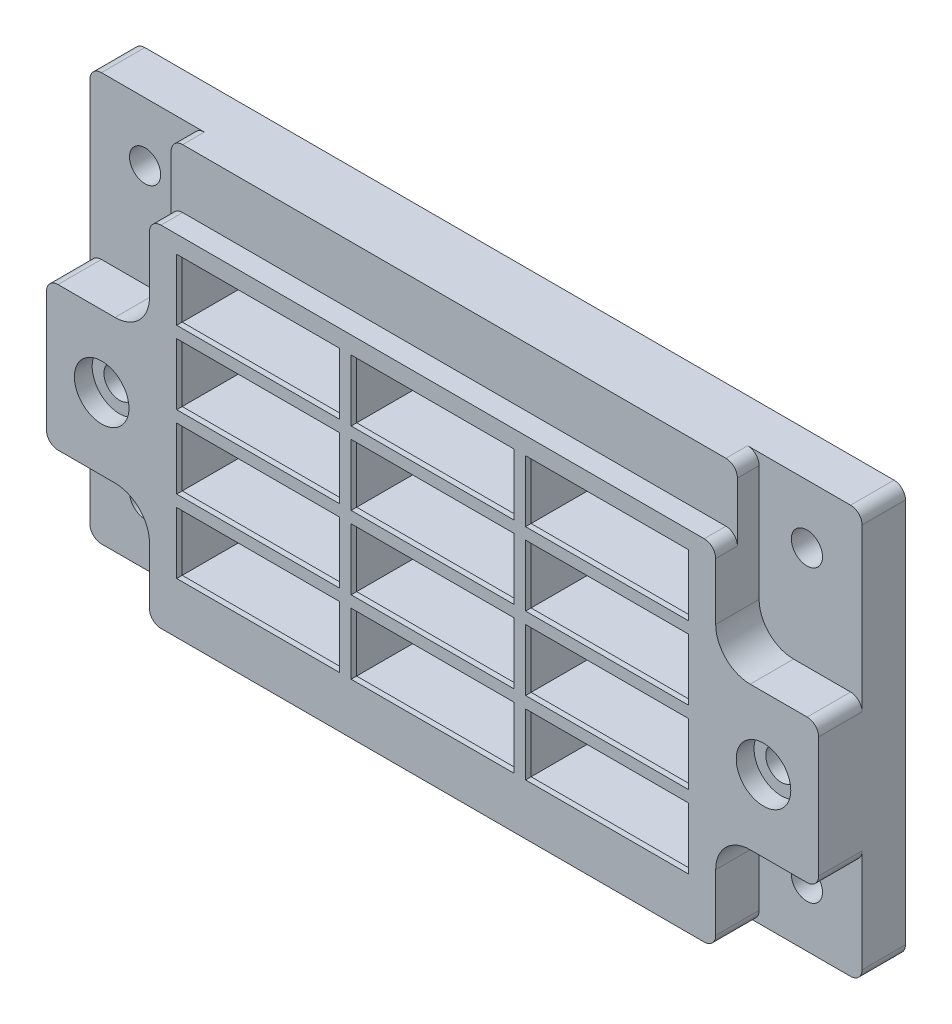
SolidWorks part; units mm, degrees
ref_plane "Front Plane" through (0, 0, 0) normal (0, 0, 1) x (1, 0, 0)
ref_plane "Top Plane" through (0, 0, 0) normal (0, 1, 0) x (1, 0, 0)
ref_plane "Right Plane" through (0, 0, 0) normal (1, 0, 0) x (0, 0, -1)
sketch "Sketch1" plane through (0, 0, 0) normal (0, 0, 1) x (1, 0, 0)
  line L4 (-3157.9913, 1122.9957) -> (-3054.4863, 1122.9957)
  line L5 (-3159.5788, 1177.7962) -> (-3159.5788, 1124.5832)
  line L6 (-3054.4863, 1179.3837) -> (-3157.9913, 1179.3837)
  line L7 (-3052.8988, 1124.5832) -> (-3052.8988, 1177.7962)
  line L8 (-3157.9913, 1122.9957) -> (-3054.4863, 1122.9957)
  line L9 (-3159.5788, 1177.7962) -> (-3159.5788, 1124.5832)
  line L10 (-3054.4863, 1179.3837) -> (-3157.9913, 1179.3837)
  line L11 (-3052.8988, 1124.5832) -> (-3052.8988, 1177.7962)
  arc A4 (-3159.5788, 1124.5832) -> (-3157.9913, 1122.9957) centre (-3157.9913, 1124.5832) ccw
  arc A5 (-3157.9913, 1179.3837) -> (-3159.5788, 1177.7962) centre (-3157.9913, 1177.7962) ccw
  arc A6 (-3052.8988, 1177.7962) -> (-3054.4863, 1179.3837) centre (-3054.4863, 1177.7962) ccw
  arc A7 (-3054.4863, 1122.9957) -> (-3052.8988, 1124.5832) centre (-3054.4863, 1124.5832) ccw
  arc A8 (-3159.5788, 1124.5832) -> (-3157.9913, 1122.9957) centre (-3157.9913, 1124.5832) ccw
  arc A9 (-3157.9913, 1179.3837) -> (-3159.5788, 1177.7962) centre (-3157.9913, 1177.7962) ccw
  arc A10 (-3052.8988, 1177.7962) -> (-3054.4863, 1179.3837) centre (-3054.4863, 1177.7962) ccw
  arc A11 (-3054.4863, 1122.9957) -> (-3052.8988, 1124.5832) centre (-3054.4863, 1124.5832) ccw
  dimension "D1" = 0
extrude "Boss-Extrude1" add sketch "Sketch1" along normal up to surface (6 mm away)
sketch "Sketch2" plane through (0, 0, 6) normal (0, 0, 1) x (1, 0, 0)
  line L0 (-3143.7673, 1122.9957) -> (-3068.7103, 1122.9957) construction
  line L1 (-3067.1228, 1124.5832) -> (-3067.1228, 1132.4572) construction
  line L2 (-3062.3603, 1137.2197) -> (-3054.4863, 1137.2197) construction
  line L3 (-3052.8988, 1138.8072) -> (-3052.8988, 1155.4442) construction
  line L4 (-3054.4863, 1157.0317) -> (-3062.3603, 1157.0317) construction
  line L5 (-3067.1228, 1161.7942) -> (-3067.1228, 1169.6682) construction
  line L7 (-3145.3548, 1169.6682) -> (-3145.3548, 1161.7942) construction
  line L8 (-3150.1173, 1157.0317) -> (-3157.9913, 1157.0317) construction
  line L9 (-3159.5788, 1155.4442) -> (-3159.5788, 1138.8072) construction
  line L10 (-3157.9913, 1137.2197) -> (-3150.1173, 1137.2197) construction
  line L11 (-3145.3548, 1132.4572) -> (-3145.3548, 1124.5832) construction
  line L12 (-3067.1228, 1169.6682) -> (-3067.1228, 1177.7962) construction
  line L13 (-3068.7103, 1179.3837) -> (-3143.7673, 1179.3837) construction
  line L14 (-3145.3548, 1177.7962) -> (-3145.3548, 1169.6682) construction
  line L16 (-3143.7673, 1122.9957) -> (-3068.7103, 1122.9957)
  line L17 (-3067.1228, 1124.5832) -> (-3067.1228, 1132.4572)
  line L18 (-3062.3603, 1137.2197) -> (-3054.4863, 1137.2197)
  line L19 (-3052.8988, 1138.8072) -> (-3052.8988, 1155.4442)
  line L20 (-3054.4863, 1157.0317) -> (-3062.3603, 1157.0317)
  line L21 (-3067.1228, 1161.7942) -> (-3067.1228, 1169.6682)
  line L23 (-3145.3548, 1169.6682) -> (-3145.3548, 1161.7942)
  line L24 (-3150.1173, 1157.0317) -> (-3157.9913, 1157.0317)
  line L25 (-3159.5788, 1155.4442) -> (-3159.5788, 1138.8072)
  line L26 (-3157.9913, 1137.2197) -> (-3150.1173, 1137.2197)
  line L27 (-3145.3548, 1132.4572) -> (-3145.3548, 1124.5832)
  line L28 (-3067.1228, 1169.6682) -> (-3067.1228, 1177.7962)
  line L29 (-3068.7103, 1179.3837) -> (-3143.7673, 1179.3837)
  line L30 (-3145.3548, 1177.7962) -> (-3145.3548, 1169.6682)
  arc A0 (-3145.3548, 1124.5832) -> (-3143.7673, 1122.9957) centre (-3143.7673, 1124.5832) ccw construction
  arc A1 (-3068.7103, 1122.9957) -> (-3067.1228, 1124.5832) centre (-3068.7103, 1124.5832) ccw construction
  arc A2 (-3062.3603, 1137.2197) -> (-3067.1228, 1132.4572) centre (-3062.3603, 1132.4572) ccw construction
  arc A3 (-3054.4863, 1137.2197) -> (-3052.8988, 1138.8072) centre (-3054.4863, 1138.8072) ccw construction
  arc A4 (-3052.8988, 1155.4442) -> (-3054.4863, 1157.0317) centre (-3054.4863, 1155.4442) ccw construction
  arc A5 (-3067.1228, 1161.7942) -> (-3062.3603, 1157.0317) centre (-3062.3603, 1161.7942) ccw construction
  arc A8 (-3150.1173, 1157.0317) -> (-3145.3548, 1161.7942) centre (-3150.1173, 1161.7942) ccw construction
  arc A9 (-3157.9913, 1157.0317) -> (-3159.5788, 1155.4442) centre (-3157.9913, 1155.4442) ccw construction
  arc A10 (-3159.5788, 1138.8072) -> (-3157.9913, 1137.2197) centre (-3157.9913, 1138.8072) ccw construction
  arc A11 (-3145.3548, 1132.4572) -> (-3150.1173, 1137.2197) centre (-3150.1173, 1132.4572) ccw construction
  arc A13 (-3067.1228, 1177.7962) -> (-3068.7103, 1179.3837) centre (-3068.7103, 1177.7962) ccw construction
  arc A14 (-3143.7673, 1179.3837) -> (-3145.3548, 1177.7962) centre (-3143.7673, 1177.7962) ccw construction
  arc A16 (-3145.3548, 1124.5832) -> (-3143.7673, 1122.9957) centre (-3143.7673, 1124.5832) ccw
  arc A17 (-3068.7103, 1122.9957) -> (-3067.1228, 1124.5832) centre (-3068.7103, 1124.5832) ccw
  arc A18 (-3062.3603, 1137.2197) -> (-3067.1228, 1132.4572) centre (-3062.3603, 1132.4572) ccw
  arc A19 (-3054.4863, 1137.2197) -> (-3052.8988, 1138.8072) centre (-3054.4863, 1138.8072) ccw
  arc A20 (-3052.8988, 1155.4442) -> (-3054.4863, 1157.0317) centre (-3054.4863, 1155.4442) ccw
  arc A21 (-3067.1228, 1161.7942) -> (-3062.3603, 1157.0317) centre (-3062.3603, 1161.7942) ccw
  arc A24 (-3150.1173, 1157.0317) -> (-3145.3548, 1161.7942) centre (-3150.1173, 1161.7942) ccw
  arc A25 (-3157.9913, 1157.0317) -> (-3159.5788, 1155.4442) centre (-3157.9913, 1155.4442) ccw
  arc A26 (-3159.5788, 1138.8072) -> (-3157.9913, 1137.2197) centre (-3157.9913, 1138.8072) ccw
  arc A27 (-3145.3548, 1132.4572) -> (-3150.1173, 1137.2197) centre (-3150.1173, 1132.4572) ccw
  arc A29 (-3067.1228, 1177.7962) -> (-3068.7103, 1179.3837) centre (-3068.7103, 1177.7962) ccw
  arc A30 (-3143.7673, 1179.3837) -> (-3145.3548, 1177.7962) centre (-3143.7673, 1177.7962) ccw
extrude "Boss-Extrude2" add sketch "Sketch2" along normal up to surface (3 mm away)
sketch "Sketch3" plane through (0, 0, 9) normal (0, 0, 1) x (1, 0, 0)
  line L12 (-3143.7673, 1122.9957) -> (-3068.7103, 1122.9957)
  line L13 (-3067.1228, 1124.5832) -> (-3067.1228, 1132.4572)
  line L14 (-3062.3603, 1137.2197) -> (-3054.4863, 1137.2197)
  line L15 (-3052.8988, 1138.8072) -> (-3052.8988, 1155.4442)
  line L16 (-3054.4863, 1157.0317) -> (-3062.3603, 1157.0317)
  line L17 (-3067.1228, 1161.7942) -> (-3067.1228, 1169.6682)
  line L18 (-3068.7103, 1171.2557) -> (-3143.7673, 1171.2557)
  line L19 (-3145.3548, 1169.6682) -> (-3145.3548, 1161.7942)
  line L20 (-3150.1173, 1157.0317) -> (-3157.9913, 1157.0317)
  line L21 (-3159.5788, 1155.4442) -> (-3159.5788, 1138.8072)
  line L22 (-3157.9913, 1137.2197) -> (-3150.1173, 1137.2197)
  line L23 (-3145.3548, 1132.4572) -> (-3145.3548, 1124.5832)
  line L24 (-3143.7673, 1122.9957) -> (-3068.7103, 1122.9957)
  line L25 (-3067.1228, 1124.5832) -> (-3067.1228, 1132.4572)
  line L26 (-3062.3603, 1137.2197) -> (-3054.4863, 1137.2197)
  line L27 (-3052.8988, 1138.8072) -> (-3052.8988, 1155.4442)
  line L28 (-3054.4863, 1157.0317) -> (-3062.3603, 1157.0317)
  line L29 (-3067.1228, 1161.7942) -> (-3067.1228, 1169.6682)
  line L30 (-3068.7103, 1171.2557) -> (-3143.7673, 1171.2557)
  line L31 (-3145.3548, 1169.6682) -> (-3145.3548, 1161.7942)
  line L32 (-3150.1173, 1157.0317) -> (-3157.9913, 1157.0317)
  line L33 (-3159.5788, 1155.4442) -> (-3159.5788, 1138.8072)
  line L34 (-3157.9913, 1137.2197) -> (-3150.1173, 1137.2197)
  line L35 (-3145.3548, 1132.4572) -> (-3145.3548, 1124.5832)
  arc A12 (-3145.3548, 1124.5832) -> (-3143.7673, 1122.9957) centre (-3143.7673, 1124.5832) ccw
  arc A13 (-3068.7103, 1122.9957) -> (-3067.1228, 1124.5832) centre (-3068.7103, 1124.5832) ccw
  arc A14 (-3062.3603, 1137.2197) -> (-3067.1228, 1132.4572) centre (-3062.3603, 1132.4572) ccw
  arc A15 (-3054.4863, 1137.2197) -> (-3052.8988, 1138.8072) centre (-3054.4863, 1138.8072) ccw
  arc A16 (-3052.8988, 1155.4442) -> (-3054.4863, 1157.0317) centre (-3054.4863, 1155.4442) ccw
  arc A17 (-3067.1228, 1161.7942) -> (-3062.3603, 1157.0317) centre (-3062.3603, 1161.7942) ccw
  arc A18 (-3067.1228, 1169.6682) -> (-3068.7103, 1171.2557) centre (-3068.7103, 1169.6682) ccw
  arc A19 (-3143.7673, 1171.2557) -> (-3145.3548, 1169.6682) centre (-3143.7673, 1169.6682) ccw
  arc A20 (-3150.1173, 1157.0317) -> (-3145.3548, 1161.7942) centre (-3150.1173, 1161.7942) ccw
  arc A21 (-3157.9913, 1157.0317) -> (-3159.5788, 1155.4442) centre (-3157.9913, 1155.4442) ccw
  arc A22 (-3159.5788, 1138.8072) -> (-3157.9913, 1137.2197) centre (-3157.9913, 1138.8072) ccw
  arc A23 (-3145.3548, 1132.4572) -> (-3150.1173, 1137.2197) centre (-3150.1173, 1132.4572) ccw
  arc A24 (-3145.3548, 1124.5832) -> (-3143.7673, 1122.9957) centre (-3143.7673, 1124.5832) ccw
  arc A25 (-3068.7103, 1122.9957) -> (-3067.1228, 1124.5832) centre (-3068.7103, 1124.5832) ccw
  arc A26 (-3062.3603, 1137.2197) -> (-3067.1228, 1132.4572) centre (-3062.3603, 1132.4572) ccw
  arc A27 (-3054.4863, 1137.2197) -> (-3052.8988, 1138.8072) centre (-3054.4863, 1138.8072) ccw
  arc A28 (-3052.8988, 1155.4442) -> (-3054.4863, 1157.0317) centre (-3054.4863, 1155.4442) ccw
  arc A29 (-3067.1228, 1161.7942) -> (-3062.3603, 1157.0317) centre (-3062.3603, 1161.7942) ccw
  arc A30 (-3067.1228, 1169.6682) -> (-3068.7103, 1171.2557) centre (-3068.7103, 1169.6682) ccw
  arc A31 (-3143.7673, 1171.2557) -> (-3145.3548, 1169.6682) centre (-3143.7673, 1169.6682) ccw
  arc A32 (-3150.1173, 1157.0317) -> (-3145.3548, 1161.7942) centre (-3150.1173, 1161.7942) ccw
  arc A33 (-3157.9913, 1157.0317) -> (-3159.5788, 1155.4442) centre (-3157.9913, 1155.4442) ccw
  arc A34 (-3159.5788, 1138.8072) -> (-3157.9913, 1137.2197) centre (-3157.9913, 1138.8072) ccw
  arc A35 (-3145.3548, 1132.4572) -> (-3150.1173, 1137.2197) centre (-3150.1173, 1132.4572) ccw
  dimension "D1" = 0
extrude "Boss-Extrude3" add sketch "Sketch3" along normal up to surface (3 mm away)
sketch "Sketch4" plane through (0, 0, 12) normal (0, 0, 1) x (1, 0, 0)
  line L0 (-3070.8888, 1130.0557) -> (-3070.8888, 1138.5557) construction
  line L1 (-3070.8888, 1138.5557) -> (-3093.3888, 1138.5557) construction
  line L2 (-3093.3888, 1138.5557) -> (-3093.3888, 1130.0557) construction
  line L3 (-3093.3888, 1130.0557) -> (-3070.8888, 1130.0557) construction
  line L4 (-3094.9888, 1138.5557) -> (-3117.4888, 1138.5557) construction
  line L5 (-3117.4888, 1138.5557) -> (-3117.4888, 1130.0557) construction
  line L6 (-3117.4888, 1130.0557) -> (-3094.9888, 1130.0557) construction
  line L7 (-3094.9888, 1130.0557) -> (-3094.9888, 1138.5557) construction
  line L8 (-3119.0888, 1138.5557) -> (-3141.5888, 1138.5557) construction
  line L9 (-3141.5888, 1138.5557) -> (-3141.5888, 1130.0557) construction
  line L10 (-3141.5888, 1130.0557) -> (-3119.0888, 1130.0557) construction
  line L11 (-3119.0888, 1130.0557) -> (-3119.0888, 1138.5557) construction
  line L12 (-3119.0888, 1140.1557) -> (-3119.0888, 1148.6557) construction
  line L13 (-3119.0888, 1148.6557) -> (-3141.5888, 1148.6557) construction
  line L14 (-3141.5888, 1148.6557) -> (-3141.5888, 1140.1557) construction
  line L15 (-3141.5888, 1140.1557) -> (-3119.0888, 1140.1557) construction
  line L16 (-3094.9888, 1140.1557) -> (-3094.9888, 1148.6557) construction
  line L17 (-3094.9888, 1148.6557) -> (-3117.4888, 1148.6557) construction
  line L18 (-3117.4888, 1148.6557) -> (-3117.4888, 1140.1557) construction
  line L19 (-3117.4888, 1140.1557) -> (-3094.9888, 1140.1557) construction
  line L20 (-3070.8888, 1148.6557) -> (-3093.3888, 1148.6557) construction
  line L21 (-3093.3888, 1148.6557) -> (-3093.3888, 1140.1557) construction
  line L22 (-3093.3888, 1140.1557) -> (-3070.8888, 1140.1557) construction
  line L23 (-3070.8888, 1140.1557) -> (-3070.8888, 1148.6557) construction
  line L24 (-3070.8888, 1158.7557) -> (-3093.3888, 1158.7557) construction
  line L25 (-3093.3888, 1158.7557) -> (-3093.3888, 1150.2557) construction
  line L26 (-3093.3888, 1150.2557) -> (-3070.8888, 1150.2557) construction
  line L27 (-3070.8888, 1150.2557) -> (-3070.8888, 1158.7557) construction
  line L28 (-3094.9888, 1150.2557) -> (-3094.9888, 1158.7557) construction
  line L29 (-3094.9888, 1158.7557) -> (-3117.4888, 1158.7557) construction
  line L30 (-3117.4888, 1158.7557) -> (-3117.4888, 1150.2557) construction
  line L31 (-3117.4888, 1150.2557) -> (-3094.9888, 1150.2557) construction
  line L32 (-3119.0888, 1150.2557) -> (-3119.0888, 1158.7557) construction
  line L33 (-3119.0888, 1158.7557) -> (-3141.5888, 1158.7557) construction
  line L34 (-3141.5888, 1158.7557) -> (-3141.5888, 1150.2557) construction
  line L35 (-3141.5888, 1150.2557) -> (-3119.0888, 1150.2557) construction
  line L36 (-3119.0888, 1160.3557) -> (-3119.0888, 1168.8557) construction
  line L37 (-3119.0888, 1168.8557) -> (-3141.5888, 1168.8557) construction
  line L38 (-3141.5888, 1168.8557) -> (-3141.5888, 1160.3557) construction
  line L39 (-3141.5888, 1160.3557) -> (-3119.0888, 1160.3557) construction
  line L40 (-3094.9888, 1160.3557) -> (-3094.9888, 1168.8557) construction
  line L41 (-3094.9888, 1168.8557) -> (-3117.4888, 1168.8557) construction
  line L42 (-3117.4888, 1168.8557) -> (-3117.4888, 1160.3557) construction
  line L43 (-3117.4888, 1160.3557) -> (-3094.9888, 1160.3557) construction
  line L44 (-3070.8888, 1168.8557) -> (-3093.3888, 1168.8557) construction
  line L45 (-3093.3888, 1168.8557) -> (-3093.3888, 1160.3557) construction
  line L46 (-3093.3888, 1160.3557) -> (-3070.8888, 1160.3557) construction
  line L47 (-3070.8888, 1160.3557) -> (-3070.8888, 1168.8557) construction
  line L48 (-3070.8888, 1130.0557) -> (-3070.8888, 1138.5557)
  line L49 (-3070.8888, 1138.5557) -> (-3093.3888, 1138.5557)
  line L50 (-3093.3888, 1138.5557) -> (-3093.3888, 1130.0557)
  line L51 (-3093.3888, 1130.0557) -> (-3070.8888, 1130.0557)
  line L52 (-3094.9888, 1138.5557) -> (-3117.4888, 1138.5557)
  line L53 (-3117.4888, 1138.5557) -> (-3117.4888, 1130.0557)
  line L54 (-3117.4888, 1130.0557) -> (-3094.9888, 1130.0557)
  line L55 (-3094.9888, 1130.0557) -> (-3094.9888, 1138.5557)
  line L56 (-3119.0888, 1138.5557) -> (-3141.5888, 1138.5557)
  line L57 (-3141.5888, 1138.5557) -> (-3141.5888, 1130.0557)
  line L58 (-3141.5888, 1130.0557) -> (-3119.0888, 1130.0557)
  line L59 (-3119.0888, 1130.0557) -> (-3119.0888, 1138.5557)
  line L60 (-3119.0888, 1140.1557) -> (-3119.0888, 1148.6557)
  line L61 (-3119.0888, 1148.6557) -> (-3141.5888, 1148.6557)
  line L62 (-3141.5888, 1148.6557) -> (-3141.5888, 1140.1557)
  line L63 (-3141.5888, 1140.1557) -> (-3119.0888, 1140.1557)
  line L64 (-3094.9888, 1140.1557) -> (-3094.9888, 1148.6557)
  line L65 (-3094.9888, 1148.6557) -> (-3117.4888, 1148.6557)
  line L66 (-3117.4888, 1148.6557) -> (-3117.4888, 1140.1557)
  line L67 (-3117.4888, 1140.1557) -> (-3094.9888, 1140.1557)
  line L68 (-3070.8888, 1148.6557) -> (-3093.3888, 1148.6557)
  line L69 (-3093.3888, 1148.6557) -> (-3093.3888, 1140.1557)
  line L70 (-3093.3888, 1140.1557) -> (-3070.8888, 1140.1557)
  line L71 (-3070.8888, 1140.1557) -> (-3070.8888, 1148.6557)
  line L72 (-3070.8888, 1158.7557) -> (-3093.3888, 1158.7557)
  line L73 (-3093.3888, 1158.7557) -> (-3093.3888, 1150.2557)
  line L74 (-3093.3888, 1150.2557) -> (-3070.8888, 1150.2557)
  line L75 (-3070.8888, 1150.2557) -> (-3070.8888, 1158.7557)
  line L76 (-3094.9888, 1150.2557) -> (-3094.9888, 1158.7557)
  line L77 (-3094.9888, 1158.7557) -> (-3117.4888, 1158.7557)
  line L78 (-3117.4888, 1158.7557) -> (-3117.4888, 1150.2557)
  line L79 (-3117.4888, 1150.2557) -> (-3094.9888, 1150.2557)
  line L80 (-3119.0888, 1150.2557) -> (-3119.0888, 1158.7557)
  line L81 (-3119.0888, 1158.7557) -> (-3141.5888, 1158.7557)
  line L82 (-3141.5888, 1158.7557) -> (-3141.5888, 1150.2557)
  line L83 (-3141.5888, 1150.2557) -> (-3119.0888, 1150.2557)
  line L84 (-3119.0888, 1160.3557) -> (-3119.0888, 1168.8557)
  line L85 (-3119.0888, 1168.8557) -> (-3141.5888, 1168.8557)
  line L86 (-3141.5888, 1168.8557) -> (-3141.5888, 1160.3557)
  line L87 (-3141.5888, 1160.3557) -> (-3119.0888, 1160.3557)
  line L88 (-3094.9888, 1160.3557) -> (-3094.9888, 1168.8557)
  line L89 (-3094.9888, 1168.8557) -> (-3117.4888, 1168.8557)
  line L90 (-3117.4888, 1168.8557) -> (-3117.4888, 1160.3557)
  line L91 (-3117.4888, 1160.3557) -> (-3094.9888, 1160.3557)
  line L92 (-3070.8888, 1168.8557) -> (-3093.3888, 1168.8557)
  line L93 (-3093.3888, 1168.8557) -> (-3093.3888, 1160.3557)
  line L94 (-3093.3888, 1160.3557) -> (-3070.8888, 1160.3557)
  line L95 (-3070.8888, 1160.3557) -> (-3070.8888, 1168.8557)
extrude "Cut-Extrude1" cut sketch "Sketch4" against normal through all
hole_wizard "#6 Clearance Hole1" positions "Sketch6" profile "Sketch5" hole size "#6" standard "ANSI Inch" end condition through all
sketch "Sketch6" plane through (0, 0, 6) normal (0, 0, 1) x (1, 0, 0)
  point P0 (-3060.5188, 1131.1237)
  point P3 (-3151.9588, 1131.1237)
  point P6 (-3151.9588, 1171.2557)
  point P9 (-3060.5188, 1171.2557)
sketch "Sketch5" plane through (-3060.5188, 1131.1237, 6) normal (1, 0, 0) x (0, -1, 0)
  line L0 (0, 0) -> (0, 6)
  line L1 (0, 6) -> (2.1526, 6)
  line L2 (2.1526, 6) -> (2.1526, 0)
  line L5 (2.1526, 0) -> (0, 0)
  line L11 (0, -6.35) -> (0, 107.95) construction
  dimension "Thru Hole Dia." = 4.3053
  dimension "Thru Hole Depth" = 6
hole_wizard "CBORE for #6 Pan Head Machine Screw1" positions "Sketch8" profile "Sketch7" counterbore size "#6" standard "ANSI Inch" end condition through all
sketch "Sketch8" plane through (0, 0, 12) normal (0, 0, 1) x (1, 0, 0)
  point P0 (-3060.5188, 1147.1257)
  point P3 (-3151.9588, 1147.1257)
sketch "Sketch7" plane through (-3060.5188, 1147.1257, 12) normal (1, 0, 0) x (0, -1, 0)
  line L0 (0, 0) -> (0, 12)
  line L1 (0, 12) -> (2.1527, 12)
  line L3 (2.1527, 12) -> (2.1527, 2.4638)
  line L4 (2.1527, 2.4638) -> (3.7706, 2.4638)
  line L5 (3.7706, 2.4638) -> (3.7706, 0)
  line L7 (3.7706, 0) -> (0, 0)
  line L11 (0, -6.35) -> (0, 107.95) construction
  dimension "Thru Hole Dia." = 4.3053
  dimension "Thru Hole Depth" = 12
  dimension "C'Bore Dia." = 7.5413
  dimension "C'Bore Depth" = 2.4638
sketch "Sketch10" plane through (0, 0, 0) normal (0, 0, -1) x (-1, 0, 0)
  line L0 (3142.0968, 1139.0637) -> (3118.5808, 1139.0637)
  line L1 (3118.5808, 1139.0637) -> (3118.5808, 1129.5477)
  line L2 (3118.5808, 1129.5477) -> (3142.0968, 1129.5477)
  line L3 (3142.0968, 1129.5477) -> (3142.0968, 1139.0637)
  line L4 (3141.5888, 1138.5557) -> (3119.0888, 1138.5557)
  line L5 (3141.5888, 1130.0557) -> (3141.5888, 1138.5557)
  line L6 (3119.0888, 1130.0557) -> (3141.5888, 1130.0557)
  line L7 (3119.0888, 1138.5557) -> (3119.0888, 1130.0557)
  line L8 (3141.5888, 1138.5557) -> (3119.0888, 1138.5557)
  line L9 (3141.5888, 1130.0557) -> (3141.5888, 1138.5557)
  line L10 (3119.0888, 1130.0557) -> (3141.5888, 1130.0557)
  line L11 (3119.0888, 1138.5557) -> (3119.0888, 1130.0557)
  line L12 (3117.4888, 1138.5557) -> (3094.9888, 1138.5557)
  line L13 (3117.4888, 1130.0557) -> (3117.4888, 1138.5557)
  line L14 (3094.9888, 1130.0557) -> (3117.4888, 1130.0557)
  line L15 (3094.9888, 1138.5557) -> (3094.9888, 1130.0557)
  line L16 (3117.4888, 1138.5557) -> (3094.9888, 1138.5557)
  line L17 (3117.4888, 1130.0557) -> (3117.4888, 1138.5557)
  line L18 (3094.9888, 1130.0557) -> (3117.4888, 1130.0557)
  line L19 (3094.9888, 1138.5557) -> (3094.9888, 1130.0557)
  line L20 (3070.8888, 1138.5557) -> (3070.8888, 1130.0557)
  line L21 (3093.3888, 1138.5557) -> (3070.8888, 1138.5557)
  line L22 (3093.3888, 1130.0557) -> (3093.3888, 1138.5557)
  line L23 (3070.8888, 1130.0557) -> (3093.3888, 1130.0557)
  line L24 (3070.8888, 1138.5557) -> (3070.8888, 1130.0557)
  line L25 (3093.3888, 1138.5557) -> (3070.8888, 1138.5557)
  line L26 (3093.3888, 1130.0557) -> (3093.3888, 1138.5557)
  line L27 (3070.8888, 1130.0557) -> (3093.3888, 1130.0557)
  line L28 (3093.3888, 1158.7557) -> (3070.8888, 1158.7557)
  line L29 (3093.3888, 1150.2557) -> (3093.3888, 1158.7557)
  line L30 (3070.8888, 1150.2557) -> (3093.3888, 1150.2557)
  line L31 (3070.8888, 1158.7557) -> (3070.8888, 1150.2557)
  line L32 (3093.3888, 1158.7557) -> (3070.8888, 1158.7557)
  line L33 (3093.3888, 1150.2557) -> (3093.3888, 1158.7557)
  line L34 (3070.8888, 1150.2557) -> (3093.3888, 1150.2557)
  line L35 (3070.8888, 1158.7557) -> (3070.8888, 1150.2557)
  line L36 (3093.3888, 1148.6557) -> (3070.8888, 1148.6557)
  line L37 (3093.3888, 1140.1557) -> (3093.3888, 1148.6557)
  line L38 (3070.8888, 1140.1557) -> (3093.3888, 1140.1557)
  line L39 (3070.8888, 1148.6557) -> (3070.8888, 1140.1557)
  line L40 (3093.3888, 1148.6557) -> (3070.8888, 1148.6557)
  line L41 (3093.3888, 1140.1557) -> (3093.3888, 1148.6557)
  line L42 (3070.8888, 1140.1557) -> (3093.3888, 1140.1557)
  line L43 (3070.8888, 1148.6557) -> (3070.8888, 1140.1557)
  line L44 (3117.4888, 1148.6557) -> (3094.9888, 1148.6557)
  line L45 (3117.4888, 1140.1557) -> (3117.4888, 1148.6557)
  line L46 (3094.9888, 1140.1557) -> (3117.4888, 1140.1557)
  line L47 (3094.9888, 1148.6557) -> (3094.9888, 1140.1557)
  line L48 (3117.4888, 1148.6557) -> (3094.9888, 1148.6557)
  line L49 (3117.4888, 1140.1557) -> (3117.4888, 1148.6557)
  line L50 (3094.9888, 1140.1557) -> (3117.4888, 1140.1557)
  line L51 (3094.9888, 1148.6557) -> (3094.9888, 1140.1557)
  line L52 (3141.5888, 1140.1557) -> (3141.5888, 1148.6557)
  line L53 (3141.5888, 1148.6557) -> (3119.0888, 1148.6557)
  line L54 (3119.0888, 1148.6557) -> (3119.0888, 1140.1557)
  line L55 (3119.0888, 1140.1557) -> (3141.5888, 1140.1557)
  line L56 (3141.5888, 1140.1557) -> (3141.5888, 1148.6557)
  line L57 (3141.5888, 1148.6557) -> (3119.0888, 1148.6557)
  line L58 (3119.0888, 1148.6557) -> (3119.0888, 1140.1557)
  line L59 (3119.0888, 1140.1557) -> (3141.5888, 1140.1557)
  line L60 (3094.9888, 1168.8557) -> (3094.9888, 1160.3557)
  line L61 (3117.4888, 1168.8557) -> (3094.9888, 1168.8557)
  line L62 (3117.4888, 1160.3557) -> (3117.4888, 1168.8557)
  line L63 (3094.9888, 1160.3557) -> (3117.4888, 1160.3557)
  line L64 (3094.9888, 1168.8557) -> (3094.9888, 1160.3557)
  line L65 (3117.4888, 1168.8557) -> (3094.9888, 1168.8557)
  line L66 (3117.4888, 1160.3557) -> (3117.4888, 1168.8557)
  line L67 (3094.9888, 1160.3557) -> (3117.4888, 1160.3557)
  line L68 (3119.0888, 1168.8557) -> (3119.0888, 1160.3557)
  line L69 (3141.5888, 1168.8557) -> (3119.0888, 1168.8557)
  line L70 (3141.5888, 1160.3557) -> (3141.5888, 1168.8557)
  line L71 (3119.0888, 1160.3557) -> (3141.5888, 1160.3557)
  line L72 (3119.0888, 1168.8557) -> (3119.0888, 1160.3557)
  line L73 (3141.5888, 1168.8557) -> (3119.0888, 1168.8557)
  line L74 (3141.5888, 1160.3557) -> (3141.5888, 1168.8557)
  line L75 (3119.0888, 1160.3557) -> (3141.5888, 1160.3557)
  line L76 (3141.5888, 1158.7557) -> (3119.0888, 1158.7557)
  line L77 (3141.5888, 1150.2557) -> (3141.5888, 1158.7557)
  line L78 (3119.0888, 1150.2557) -> (3141.5888, 1150.2557)
  line L79 (3119.0888, 1158.7557) -> (3119.0888, 1150.2557)
  line L80 (3141.5888, 1158.7557) -> (3119.0888, 1158.7557)
  line L81 (3141.5888, 1150.2557) -> (3141.5888, 1158.7557)
  line L82 (3119.0888, 1150.2557) -> (3141.5888, 1150.2557)
  line L83 (3119.0888, 1158.7557) -> (3119.0888, 1150.2557)
  line L84 (3117.4888, 1150.2557) -> (3117.4888, 1158.7557)
  line L85 (3117.4888, 1158.7557) -> (3094.9888, 1158.7557)
  line L86 (3094.9888, 1158.7557) -> (3094.9888, 1150.2557)
  line L87 (3094.9888, 1150.2557) -> (3117.4888, 1150.2557)
  line L88 (3117.4888, 1150.2557) -> (3117.4888, 1158.7557)
  line L89 (3117.4888, 1158.7557) -> (3094.9888, 1158.7557)
  line L90 (3094.9888, 1158.7557) -> (3094.9888, 1150.2557)
  line L91 (3094.9888, 1150.2557) -> (3117.4888, 1150.2557)
  line L92 (3070.8888, 1160.3557) -> (3093.3888, 1160.3557)
  line L93 (3093.3888, 1160.3557) -> (3093.3888, 1168.8557)
  line L94 (3093.3888, 1168.8557) -> (3070.8888, 1168.8557)
  line L95 (3070.8888, 1168.8557) -> (3070.8888, 1160.3557)
  line L96 (3070.8888, 1160.3557) -> (3093.3888, 1160.3557)
  line L97 (3093.3888, 1160.3557) -> (3093.3888, 1168.8557)
  line L98 (3093.3888, 1168.8557) -> (3070.8888, 1168.8557)
  line L99 (3070.8888, 1168.8557) -> (3070.8888, 1160.3557)
  line L100 (3117.9968, 1139.0637) -> (3094.4808, 1139.0637)
  line L101 (3094.4808, 1139.0637) -> (3094.4808, 1129.5477)
  line L102 (3094.4808, 1129.5477) -> (3117.9968, 1129.5477)
  line L103 (3117.9968, 1129.5477) -> (3117.9968, 1139.0637)
  line L104 (3070.3808, 1139.0637) -> (3070.3808, 1129.5477)
  line L105 (3070.3808, 1129.5477) -> (3093.8968, 1129.5477)
  line L106 (3093.8968, 1129.5477) -> (3093.8968, 1139.0637)
  line L107 (3093.8968, 1139.0637) -> (3070.3808, 1139.0637)
  line L108 (3093.8968, 1159.2637) -> (3070.3808, 1159.2637)
  line L109 (3070.3808, 1159.2637) -> (3070.3808, 1149.7477)
  line L110 (3070.3808, 1149.7477) -> (3093.8968, 1149.7477)
  line L111 (3093.8968, 1149.7477) -> (3093.8968, 1159.2637)
  line L112 (3093.8968, 1149.1637) -> (3070.3808, 1149.1637)
  line L113 (3070.3808, 1149.1637) -> (3070.3808, 1139.6477)
  line L114 (3070.3808, 1139.6477) -> (3093.8968, 1139.6477)
  line L115 (3093.8968, 1139.6477) -> (3093.8968, 1149.1637)
  line L116 (3117.9968, 1149.1637) -> (3094.4808, 1149.1637)
  line L117 (3094.4808, 1149.1637) -> (3094.4808, 1139.6477)
  line L118 (3094.4808, 1139.6477) -> (3117.9968, 1139.6477)
  line L119 (3117.9968, 1139.6477) -> (3117.9968, 1149.1637)
  line L120 (3142.0968, 1139.6477) -> (3142.0968, 1149.1637)
  line L121 (3142.0968, 1149.1637) -> (3118.5808, 1149.1637)
  line L122 (3118.5808, 1149.1637) -> (3118.5808, 1139.6477)
  line L123 (3118.5808, 1139.6477) -> (3142.0968, 1139.6477)
  line L124 (3094.4808, 1169.3637) -> (3094.4808, 1159.8477)
  line L125 (3094.4808, 1159.8477) -> (3117.9968, 1159.8477)
  line L126 (3117.9968, 1159.8477) -> (3117.9968, 1169.3637)
  line L127 (3117.9968, 1169.3637) -> (3094.4808, 1169.3637)
  line L128 (3118.5808, 1169.3637) -> (3118.5808, 1159.8477)
  line L129 (3118.5808, 1159.8477) -> (3142.0968, 1159.8477)
  line L130 (3142.0968, 1159.8477) -> (3142.0968, 1169.3637)
  line L131 (3142.0968, 1169.3637) -> (3118.5808, 1169.3637)
  line L132 (3142.0968, 1159.2637) -> (3118.5808, 1159.2637)
  line L133 (3118.5808, 1159.2637) -> (3118.5808, 1149.7477)
  line L134 (3118.5808, 1149.7477) -> (3142.0968, 1149.7477)
  line L135 (3142.0968, 1149.7477) -> (3142.0968, 1159.2637)
  line L136 (3117.9968, 1149.7477) -> (3117.9968, 1159.2637)
  line L137 (3117.9968, 1159.2637) -> (3094.4808, 1159.2637)
  line L138 (3094.4808, 1159.2637) -> (3094.4808, 1149.7477)
  line L139 (3094.4808, 1149.7477) -> (3117.9968, 1149.7477)
  line L140 (3070.3808, 1159.8477) -> (3093.8968, 1159.8477)
  line L141 (3093.8968, 1159.8477) -> (3093.8968, 1169.3637)
  line L142 (3093.8968, 1169.3637) -> (3070.3808, 1169.3637)
  line L143 (3070.3808, 1169.3637) -> (3070.3808, 1159.8477)
  dimension "D1" = 0
  dimension "D2" = 0
  dimension "D3" = 0
  dimension "D4" = 0
  dimension "D5" = 0
  dimension "D6" = 0
  dimension "D7" = 0
  dimension "D8" = 0
  dimension "D9" = 0
  dimension "D10" = 0
  dimension "D11" = 0
  dimension "D12" = 0
  dimension "D13" = 0.508
extrude "Cut-Extrude3" cut sketch "Sketch10" against normal offset from surface (11.238 mm away) 0.762 up to face at (-3056.7481, 1147.1257, 12)
hole_wizard "Hole1" positions "Sketch12" profile "Sketch11" legacy
sketch "Sketch12" plane through (0, 0, 0) normal (0, 0, -1) x (-1, 0, 0)
  line L0 (3118.5808, 1129.5477) -> (3142.0968, 1129.5477) construction
  line L1 (3142.0968, 1129.5477) -> (3142.0968, 1139.0637) construction
  line L2 (3106.2434, 1129.8017) -> (3106.2434, 1149.4557) construction
  line L3 (3094.7394, 1129.8017) -> (3117.7474, 1129.8017) construction
  line L4 (3106.2434, 1149.4557) -> (3070.4064, 1149.4557) construction
  line L6 (3070.3808, 1149.7477) -> (3093.8968, 1149.7477) construction
  line L7 (3093.8968, 1149.1637) -> (3070.3808, 1149.1637) construction
  point P0 (3144.6368, 1132.0877)
  point P21 (3067.85, 1132.0877)
  point P23 (3144.6368, 1166.8237)
  point P24 (3067.85, 1166.8237)
  dimension "D1" = 2.54
  dimension "D2" = 2.54
sketch "Sketch11" plane through (-3144.6368, 1132.0877, 0) normal (1, 0, 0) x (0, 1, 0)
  line L0 (0, 0) -> (0, 2.921)
  line L1 (0, 2.921) -> (1.4986, 2.921)
  line L2 (1.4986, 2.921) -> (1.6383, 0)
  line L3 (1.6383, 0) -> (0, 0)
  line L4 (0, 110) -> (0, -10) construction
  dimension "Minor Diameter" = 2.9972
  dimension "Depth" = 2.921
  dimension "Major Diameter" = 3.2766
